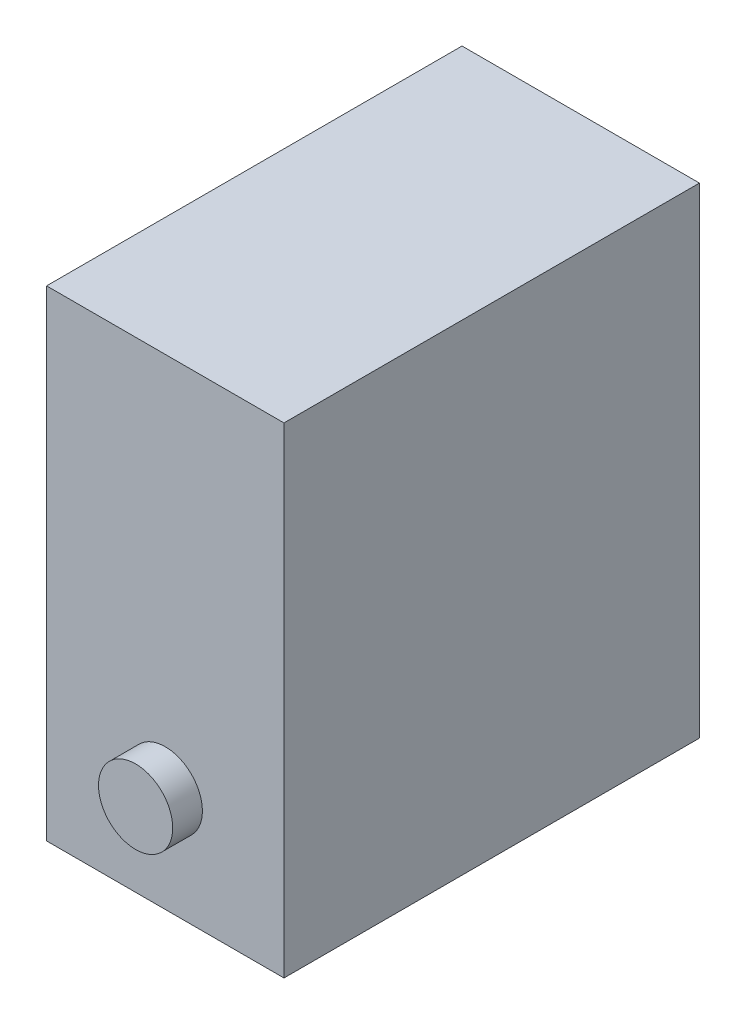
SolidWorks part; units mm, degrees
ref_plane "Front Plane" through (0, 0, 0) normal (0, 0, 1) x (1, 0, 0)
ref_plane "Top Plane" through (0, 0, 0) normal (0, 1, 0) x (1, 0, 0)
ref_plane "Right Plane" through (0, 0, 0) normal (1, 0, 0) x (0, 0, -1)
sketch "Sketch1" plane through (0, 0, 0) normal (0, 1, 0) x (1, 0, 0)
  line L1 (0, 0) -> (20.32, 0)
  line L2 (0, 0) -> (0, 35.56)
  line L3 (0, 35.56) -> (20.32, 35.56)
  line L4 (20.32, 0) -> (20.32, 35.56)
  dimension "D1" = 20.32
  dimension "D2" = 35.56
extrude "Boss-Extrude1" add sketch "Sketch1" along normal blind 41.148
sketch "Sketch2" plane through (0, 0, 0) normal (0, 0, 1) x (1, 0, 0)
  line L0 (10.16, 8.89) -> (10.16, 0) construction
  line L1 (0, 0) -> (20.32, 0) construction
  circle A0 centre (10.16, 8.89) radius 3.175
  dimension "D2" = 6.35
  dimension "D1" = 8.89
extrude "Boss-Extrude2" add sketch "Sketch2" along normal blind 2.54
